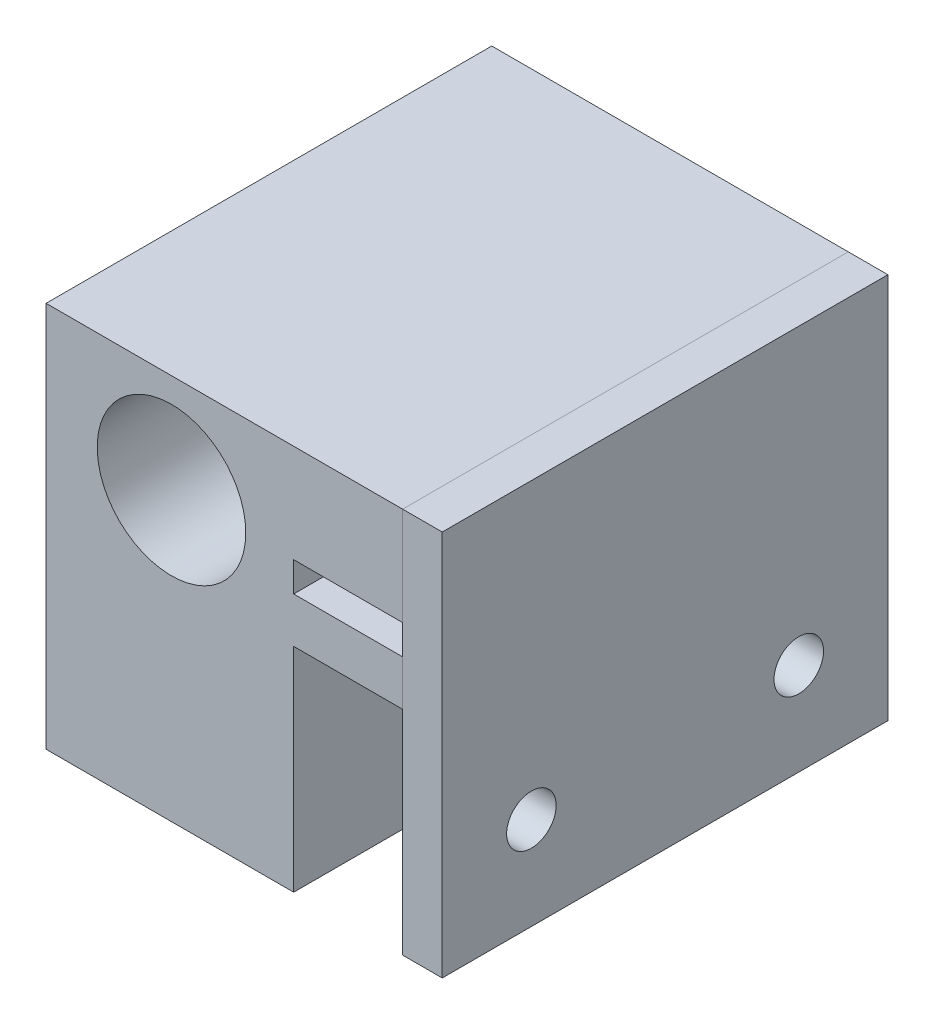
SolidWorks part; units mm, degrees
ref_plane "Front Plane" through (0, 0, 0) normal (0, 0, 1) x (1, 0, 0)
ref_plane "Top Plane" through (0, 0, 0) normal (0, 1, 0) x (1, 0, 0)
ref_plane "Right Plane" through (0, 0, 0) normal (1, 0, 0) x (0, 0, -1)
sketch "Sketch1" plane through (0, 0, 0) normal (0, 0, 1) x (1, 0, 0)
  line L5 (20, 29) -> (-20, 29)
  line L6 (20, 29) -> (20, -10)
  line L7 (20, -10) -> (-20, -10)
  line L8 (-20, 29) -> (-20, -10)
  line L9 (20, 29) -> (-20, -10) construction
  line L10 (20, -10) -> (-20, 29) construction
  circle A0 centre (-7.34, 19) radius 7.5
  point P0 (0, 9.5)
  dimension "D3" = 15
  dimension "D1" = 40
  dimension "D2" = 39
  dimension "D4" = 10
  dimension "D5" = 27.34
extrude "Boss-Extrude1" add sketch "Sketch1" against normal blind 45
sketch "Sketch3" plane through (0, -10, 0) normal (0, -1, 0) x (1, 0, 0)
  line L0 (-7.34, -0.349) -> (-7.34, -3.737) construction
  line L1 (-20, -45) -> (20, -45) construction
  line L2 (-7.34, 0) -> (-7.34, -45) construction
  line L3 (-20, 0) -> (20, 0) construction
  line L5 (-14.84, -0.349) -> (0.16, -0.349) construction
  circle A0 centre (-7.34, -11.25) radius 4
  circle A1 centre (-7.34, -33.75) radius 4
  point P5 (13.75, 0)
  dimension "D5" = 8
  dimension "D1" = 11.25
extrude "Cut-Extrude1" cut sketch "Sketch3" against normal blind 17
sketch "Sketch5" plane through (0, 0, -45) normal (0, 0, -1) x (-1, 0, 0)
  line L0 (-5, -10) -> (-5, 11.5)
  line L1 (20, -10) -> (-20, -10) construction
  line L3 (-16, 11.5) -> (-16, -10)
  line L4 (-16, -10) -> (-5, -10)
  line L5 (-20, -10) -> (-20, 29) construction
  line L7 (53, 9) -> (-447, 9) construction
  line L9 (-16, 19) -> (-5, 19) construction
  line L11 (-447, 19) -> (53, 19) construction
  line L12 (-16, 11.5) -> (-5, 11.5)
  line L13 (-16, 16.08) -> (-5, 16.08)
  line L14 (-16, 16.08) -> (-16, 19.08)
  line L15 (-16, 19.08) -> (-5, 19.08)
  line L16 (-5, 19.08) -> (-5, 16.08)
  dimension "D1" = 25
  dimension "D2" = 4
  dimension "D3" = 2.5
  dimension "D4" = 7.08
  dimension "D5" = 3
extrude "Cut-Extrude3" cut sketch "Sketch5" against normal through all
sketch "Sketch6" plane through (20, 0, 0) normal (1, 0, 0) x (0, 0, -1)
  line L1 (45, -10) -> (45, 29) construction
  line L2 (0, -10) -> (0, 29) construction
  line L6 (-288.3553, 9) -> (151.6447, 9) construction
  circle A0 centre (36, -0.65) radius 2.5
  circle A3 centre (9, -0.65) radius 2.5
  dimension "D2" = 5
  dimension "D3" = 9
  dimension "D4" = 9
  dimension "D1" = 9.65
extrude "Cut-Extrude4" cut sketch "Sketch6" against normal up to surface (4 mm away) up to face at (16, 0.75, -22.5)
ref_plane "Plane1" through (16, 0, 0) normal (-1, 0, 0) x (0, 0, 1)
split "Split1" trim tools "Plane1" bodies to split 105 resulting bodies 106 107
